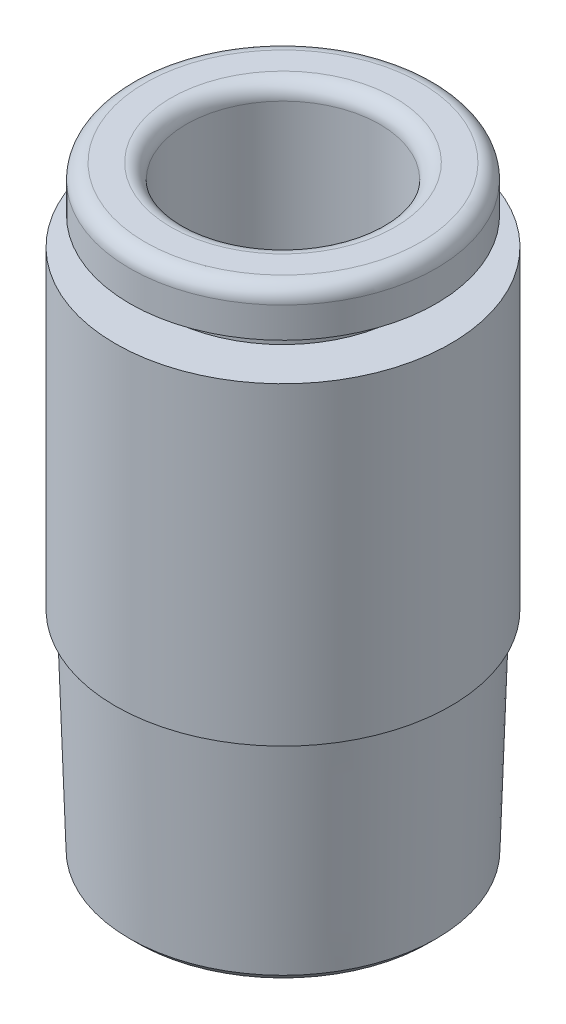
SolidWorks part; units mm, degrees
ref_plane "Front" through (0, 0, 0) normal (0, 0, 1) x (1, 0, 0)
ref_plane "Top" through (0, 0, 0) normal (0, 1, 0) x (1, 0, 0)
ref_plane "Right" through (0, 0, 0) normal (1, 0, 0) x (0, 0, -1)
ref_plane "Release_Height" through (0, -2.4, 0) normal (0, 1, 0) x (-1, 0, 0)
ref_plane "UBody_Height" through (0, -12.7, 0) normal (0, 1, 0) x (-1, 0, 0)
ref_plane "LBody_Height" through (0, -12.7, 0) normal (0, 1, 0) x (-1, 0, 0)
ref_plane "L-Total_Height" through (0, -19.8, 0) normal (0, 1, 0) x (-1, 0, 0)
ref_plane "M-Tube_Depth" through (0, -13.3, 0) normal (0, 1, 0) x (-1, 0, 0)
sketch "Release_Sketch" plane through (0, 0, 0) normal (0, 0, 1) x (1, 0, 0)
  line L0 (0, 0) -> (0, -23.4083) construction
  line L1 (0, 0) -> (-4.525, 0)
  line L2 (-5.025, -0.5) -> (-5.025, -1.5)
  line L3 (-5.025, -1.5) -> (-3.925, -1.5)
  line L4 (-3.925, -1.5) -> (-3.925, -2.4)
  line L5 (-3.925, -2.4) -> (0, -2.4)
  line L6 (14.7616, -2.4) -> (-14.7616, -2.4) construction
  line L7 (0, 0) -> (0, -2.4)
  arc A0 (-5.025, -0.5) -> (-4.525, 0) centre (-4.525, -0.5) cw
  point P12 (-5.025, 0)
  dimension "Radius" = 0.5
  dimension "Thickness" = 1.5
  dimension "Tube_Dia" = 7.85
  dimension "Outer_Dia" = 10.05
revolve "Release" add sketch "Release_Sketch" angle 360 about L0
sketch "UBody_Sketch" plane through (0, -2.4, 0) normal (0, 1, 0) x (-1, 0, 0)
  circle A0 centre (0, 0) radius 5.5
  dimension "Dia" = 11
extrude "UBody" add sketch "UBody_Sketch" against normal up to surface (10.3 mm away) up to plane "UBody_Height"
sketch "LBody_Sketch" [suppressed] plane through (0, -16, 0) normal (0, 1, 0) x (-1, 0, 0)
  circle A0 centre (0, 0) radius 3.45
  dimension "Dia" = 7.2
extrude "LBody" [suppressed] add sketch "LBody_Sketch" against normal up to surface (0.6 mm away) up to plane "LBody_Height"
chamfer "UBody_Chamfer" [suppressed] distance 1.9 angle 20
sketch "Thread_Sketch" plane through (0, 0, 0) normal (0, 0, 1) x (1, 0, 0)
  line L0 (0, 0) -> (0, -23.8143) construction
  line L1 (0, -12.7) -> (0, -2.4) construction
  line L2 (-5.2475, -12.7) -> (-5.0263, -19.8)
  line L3 (-5.0263, -19.8) -> (0, -19.8)
  line L4 (0, -19.8) -> (0, -12.7)
  line L5 (0, -12.7) -> (-5.2475, -12.7)
  line L7 (14.7616, -19.8) -> (-14.7616, -19.8) construction
  line L8 (14.7616, -12.7) -> (-14.7616, -12.7) construction
  point P13 (-5.15, -15.83)
  dimension "Taper" = 88.216
  dimension "a" = 3.97
  dimension "d" = 10.3
revolve "Thread" add sketch "Thread_Sketch" angle 360 about L0
chamfer "Thread_Chamfer" distance 0.25 angle 45 1 edges at (0, -19.8, 5.0263) first distance on face at (0, -19.8, 5.0263)
chamfer "LBody_Chamfer" [suppressed] distance 1.9 angle 45
sketch "Tube_Sketch" plane through (0, 0, 0) normal (0, 1, 0) x (1, 0, 0)
  circle A0 centre (0, 0) radius 3.175
  dimension "Dia" = 6.35
extrude "Tube" cut sketch "Tube_Sketch" against normal up to surface (13.3 mm away) up to plane "M-Tube_Depth"
fillet "Tube_Radius" radius 0.5 1 edges at (0, 0, 3.175)
sketch "Hex_Sketch" plane through (0, -13.3, 0) normal (0, 1, 0) x (-1, 0, 0)
  line L1 (-2.7482, 0) -> (-1.3741, -2.38)
  line L2 (-1.3741, -2.38) -> (1.3741, -2.38)
  line L3 (1.3741, -2.38) -> (2.7482, 0)
  line L4 (2.7482, 0) -> (1.3741, 2.38)
  line L5 (1.3741, 2.38) -> (-1.3741, 2.38)
  line L6 (-1.3741, 2.38) -> (-2.7482, 0)
  circle A0 centre (0, 0) radius 2.38 construction
  dimension "Hex" = 4.76
extrude "Hex" cut sketch "Hex_Sketch" against normal blind 2 draft 2
sketch "Port_Sketch" plane through (0, -15.3, 0) normal (0, 1, 0) x (-1, 0, 0)
  line L0 (-2.6675, 0) -> (-1.3338, -2.3102) construction
  circle A0 centre (0, 0) radius 2.3102
extrude "Port" cut sketch "Port_Sketch" against normal through all
sketch "Connecting Point" plane through (0, 0, 0) normal (0, 0, 1) x (1, 0, 0)
  line L0 (0, -12.7) -> (0, -2.4) construction
  line L1 (14.7616, 0) -> (-14.7616, 0) construction
  point P0 (0, -16.6)
  dimension "A" = 16.6
